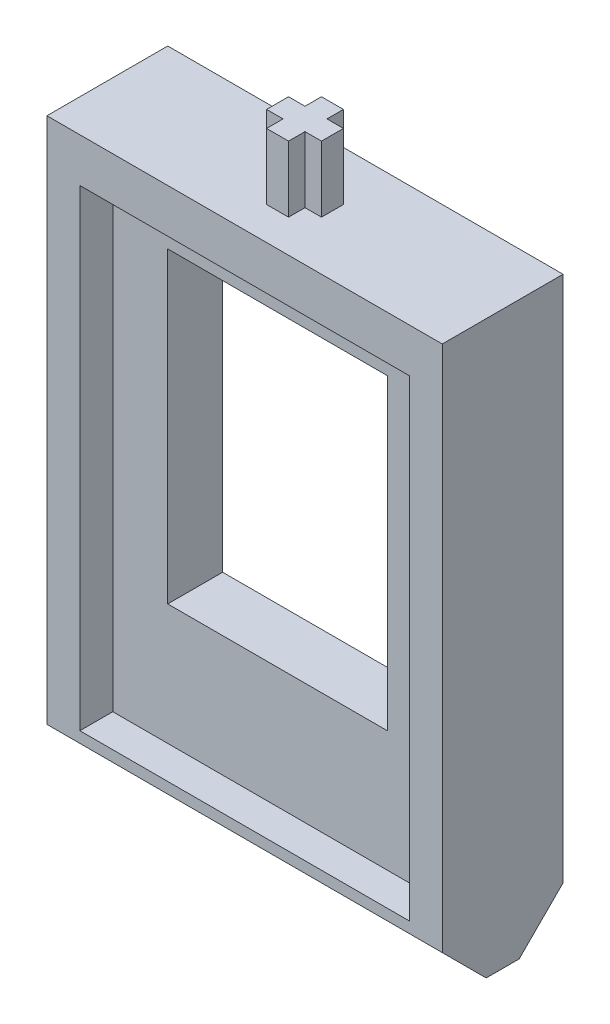
SolidWorks part; units mm, degrees
ref_plane "Front Plane" through (0, 0, 0) normal (0, 0, 1) x (1, 0, 0)
ref_plane "Top Plane" through (0, 0, 0) normal (0, 1, 0) x (1, 0, 0)
ref_plane "Right Plane" through (0, 0, 0) normal (1, 0, 0) x (0, 0, -1)
sketch "Sketch1" plane through (0, 0, 0) normal (0, 0, 1) x (1, 0, 0)
  line L1 (-9, 13) -> (9, 13)
  line L2 (-9, 13) -> (-9, -13)
  line L3 (-9, -13) -> (9, -13)
  line L4 (9, 13) -> (9, -13)
  line L5 (-9, 13) -> (9, -13) construction
  line L6 (-9, -13) -> (9, 13) construction
  point P0 (0, 0)
  dimension "D1" = 26
  dimension "D2" = 18
extrude "Boss-Extrude1" add sketch "Sketch1" along normal blind 5.5 contours L2 L3 L4 L1
sketch "Sketch2" plane through (0, 13, 0) normal (0, 1, 0) x (1, 0, 0)
  line L0 (-9, -5.5) -> (-9, 0) construction
  line L1 (-0.5, -1.5) -> (0.5, -1.5)
  line L2 (-0.5, -1.5) -> (-0.5, -2.25)
  line L3 (-0.5, -4) -> (0.5, -4)
  line L4 (0.5, -1.5) -> (0.5, -2.25)
  line L5 (-0.5, -1.5) -> (0.5, -4) construction
  line L6 (-0.5, -4) -> (0.5, -1.5) construction
  line L7 (-1.25, -2.25) -> (-0.5, -2.25)
  line L8 (-1.25, -2.25) -> (-1.25, -3.25)
  line L9 (-1.25, -3.25) -> (-0.5, -3.25)
  line L10 (1.25, -2.25) -> (1.25, -3.25)
  line L11 (-1.25, -2.25) -> (1.25, -3.25) construction
  line L12 (-1.25, -3.25) -> (1.25, -2.25) construction
  line L13 (-9, -5.5) -> (9, -5.5) construction
  line L14 (0.5, -2.25) -> (1.25, -2.25)
  line L15 (0.5, -3.25) -> (0.5, -4)
  line L16 (0.5, -3.25) -> (1.25, -3.25)
  line L17 (-0.5, -3.25) -> (-0.5, -4)
  point P0 (0, -2.75)
  point P5 (0, -2.75)
  point P10 (0, 0)
  point P13 (-9, -2.75)
  point P16 (0, -5.5)
  dimension "D1" = 2.5
  dimension "D2" = 2.5
  dimension "D3" = 1
  dimension "D4" = 1
chamfer "Chamfer1" distance 2 angle 45 2 edges at (0, -13, 0) (0, -13, 5.5)
sketch "Sketch3" plane through (0, 0, 5.5) normal (0, 0, 1) x (1, 0, 0)
  line L0 (-9, 13) -> (9, 13) construction
  line L1 (-7.5, 11) -> (7.5, 11)
  line L2 (-7.5, 11) -> (-7.5, -10.5)
  line L3 (-7.5, -10.5) -> (7.5, -10.5)
  line L4 (7.5, 11) -> (7.5, -10.5)
  line L5 (-7.5, 11) -> (7.5, -10.5) construction
  line L6 (-7.5, -10.5) -> (7.5, 11) construction
  line L7 (-9, 13) -> (-9, -11) construction
  line L8 (9, 13) -> (9, -11) construction
  line L9 (-9, -11) -> (9, -11) construction
  point P0 (0, 0.25)
  point P5 (-7.751, 11.7572)
  point P6 (7.8461, -9.7363)
  dimension "D1" = 2
  dimension "D2" = 1.5
  dimension "D3" = 1.5
  dimension "D4" = 0.5
extrude "Cut-Extrude1" cut sketch "Sketch3" against normal blind 1.5 contours L2 L3 L4 L1
ref_plane "Plane1" through (0, 0, 2.75) normal (0, 0, 1) x (1, 0, 0)
mirror "Mirror1" about plane through (0, 0, 2.75) normal (0, 0, 1) of "Cut-Extrude1"
sketch "Sketch4" plane through (0, 0, 1.5) normal (0, 0, -1) x (-1, 0, 0)
  line L0 (7.5, 11) -> (-7.5, 11) construction
  line L1 (-5, 9) -> (5, 9)
  line L2 (-5, 9) -> (-5, -5)
  line L3 (-5, -5) -> (5, -5)
  line L4 (5, 9) -> (5, -5)
  line L5 (-5, 9) -> (5, -5) construction
  line L6 (-5, -5) -> (5, 9) construction
  point P0 (0, 2)
  point P7 (0, 11)
  dimension "D1" = 14
  dimension "D2" = 10
  dimension "D3" = 2
extrude "Cut-Extrude2" cut sketch "Sketch4" against normal blind 61.5
extrude "Boss-Extrude2" add sketch "Sketch2" along normal blind 3 contours L3 L15 L16 L10 L14 L4 L1 L2 L7 L8 L9 L17
